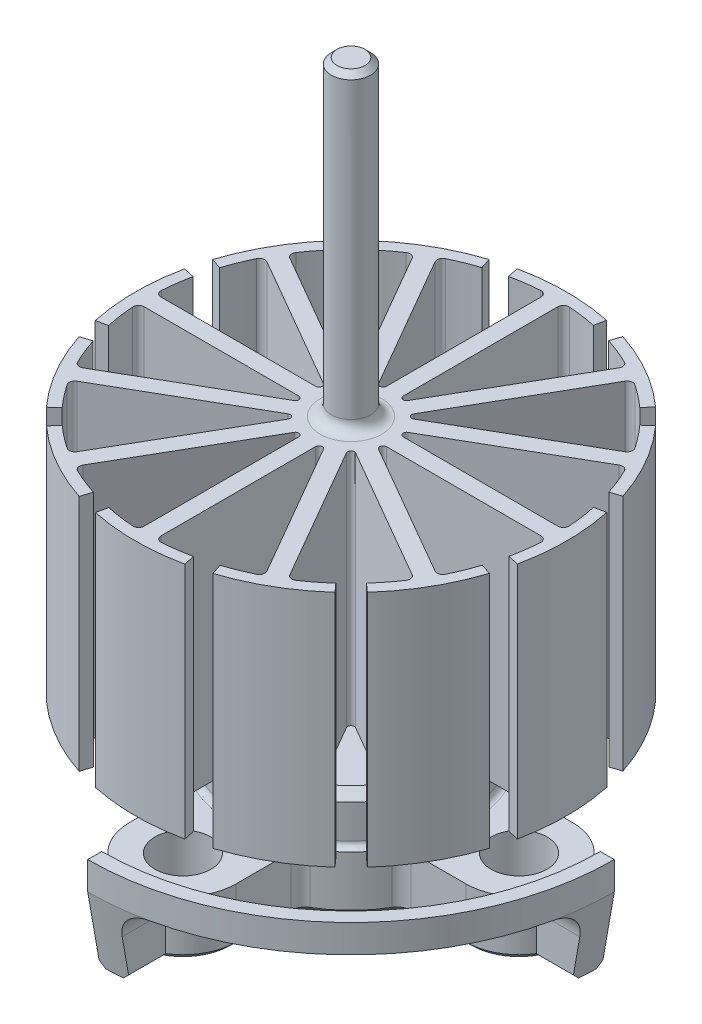
SolidWorks part; units mm, degrees
material "Ti-6Al-4V Solución tratada y envejecida (SS)"
ref_plane "Alzado" through (0, 0, 0) normal (0, 0, 1) x (1, 0, 0)
ref_plane "Planta" through (0, 0, 0) normal (0, 1, 0) x (1, 0, 0)
ref_plane "Vista lateral" through (0, 0, 0) normal (1, 0, 0) x (0, 0, -1)
sketch "Croquis1" plane through (0, 0, 0) normal (0, 0, 1) x (1, 0, 0)
  line L0 (0, 37.6231) -> (0, -37.6231) construction
  line L1 (0, -9.515) -> (0, 9.515) construction
  line L2 (9.515, 0) -> (-9.515, 0) construction
  line L3 (7.9, 0) -> (7.9, 2)
  line L4 (7.9, 2) -> (4.2, 2)
  line L5 (4, 2.2) -> (4, 3.4)
  line L6 (4, 3.4) -> (3.7, 3.7)
  line L7 (3.7, 3.7) -> (0.75, 3.7)
  line L8 (0.7, 12.9) -> (0.7, 23.6)
  line L9 (0.7, 23.6) -> (0, 23.6)
  line L10 (0, 23.6) -> (0, -1.4)
  line L11 (0.7, 0) -> (7.9, 0)
  line L12 (0.7, 0) -> (0.7, -0.2)
  line L13 (0.7, -0.2) -> (0.54, -0.2)
  line L14 (0.5, -0.24) -> (0.5, -0.41)
  line L15 (0.54, -0.45) -> (1, -0.45)
  line L16 (1, -0.45) -> (1, -1.2)
  line L17 (0.8, -1.4) -> (0, -1.4)
  line L18 (0.7, 3.75) -> (0.7, 3.95)
  line L19 (0.75, 4) -> (7.7, 4)
  line L20 (7.7, 4) -> (7.7, 12.5)
  line L21 (7.7, 12.5) -> (1.1, 12.5)
  arc A0 (4.2, 2) -> (4, 2.2) centre (4.2, 2.2) cw
  arc A1 (0.75, 3.7) -> (0.7, 3.75) centre (0.75, 3.75) cw
  arc A2 (0.54, -0.2) -> (0.5, -0.24) centre (0.54, -0.24) ccw
  arc A3 (0.5, -0.41) -> (0.54, -0.45) centre (0.54, -0.41) ccw
  arc A4 (1, -1.2) -> (0.8, -1.4) centre (0.8, -1.2) cw
  arc A5 (0.7, 3.95) -> (0.75, 4) centre (0.75, 3.95) cw
  arc A6 (0.7, 12.9) -> (1.1, 12.5) centre (1.1, 12.9) ccw
  point P5 (0, 0)
  dimension "D4" = 0.2
  dimension "D5" = 0.05
  dimension "D13" = 0.04
  dimension "D17" = 0.2
  dimension "D22" = 0.4
  dimension "D1" = 15.8
  dimension "D3" = 8
  dimension "D6" = 2
  dimension "D7" = 0.3
  dimension "D8" = 0.3
  dimension "D9" = 25
  dimension "D10" = 1.4
  dimension "D11" = 0.2
  dimension "D12" = 0.25
  dimension "D14" = 2
  dimension "D15" = 1
  dimension "D16" = 1.4
  dimension "D18" = 4
  dimension "D19" = 0.3
  dimension "D20" = 8.5
  dimension "D21" = 1.4
  dimension "D23" = 15.4
revolve "Revolución1" add sketch "Croquis1" angle 360 about L0
sketch "Croquis2" plane through (0, 12.5, 0) normal (0, 1, 0) x (1, 0, 0)
  line L0 (0, 0) -> (7.7, 0) construction
  line L1 (-9.515, 0) -> (9.515, 0) construction
  line L2 (0, 0) -> (6.6684, -3.85) construction
  line L3 (0, 0) -> (3.85, -6.6684) construction
  line L4 (0, 0) -> (0, -7.7) construction
  line L5 (0, 0) -> (-3.85, -6.6684) construction
  line L6 (0, 0) -> (-6.6684, -3.85) construction
  line L7 (0, 0) -> (-7.7, 0) construction
  line L8 (0, 0) -> (-6.6684, 3.85) construction
  line L9 (0, 0) -> (-3.85, 6.6684) construction
  line L10 (0, 0) -> (0, 7.7) construction
  line L11 (0, 0) -> (3.85, 6.6684) construction
  line L12 (0, 0) -> (6.6684, 3.85) construction
  line L13 (6.2835, 3.2814) -> (1.5044, 0.5221)
  line L14 (1.5639, 0.3) -> (7.0824, 0.3)
  line L15 (7.3201, 2.3887) -> (6.9398, 2.2647)
  line L16 (7.5319, 1.6) -> (7.1407, 1.5169)
  circle A0 centre (0, 0) radius 7.7 construction
  arc A1 (1.299, 0.75) -> (1.5, 0) centre (0, 0) ccw construction
  arc A2 (7.2819, 0.5141) -> (7.1407, 1.5169) centre (0, 0) ccw
  arc A4 (6.9398, 2.2647) -> (6.5633, 3.1957) centre (0, 0) ccw
  arc A5 (7.5319, 1.6) -> (7.3201, 2.3887) centre (0, 0) ccw
  arc A6 (1.5, 0) -> (1.299, 0.75) centre (0, 0) ccw construction
  arc A7 (1.5044, 0.5221) -> (1.5639, 0.3) centre (1.5639, 0.419) ccw
  arc A8 (7.0824, 0.3) -> (7.2819, 0.5141) centre (7.0824, 0.5) ccw
  arc A9 (6.2835, 3.2814) -> (6.5633, 3.1957) centre (6.3835, 3.1082) cw
  point P21 (0, 0)
  dimension "D2" = 3
  dimension "D8" = 0.2
  dimension "D3" = 0.3
  dimension "D4" = 0.3
  dimension "D5" = 1.6
  dimension "D6" = 1.6
  dimension "D7" = 0.4
  dimension "D1" = 12
extrude "Cortar-Extruir1" cut sketch "Croquis2" against normal up to surface (8.8 mm away) up to face at (0, 3.7, 0.75)
pattern_circular "MatrizC2" count 12 over 360 about axis through (0, 12.5, 0) along (0, 1, 0) of "Cortar-Extruir1"
sketch "Croquis6" plane through (0, 0, 0) normal (0, 0, 1) x (1, 0, 0)
  line L0 (9.4, 2.5) -> (8.9592, 0)
  line L1 (9.4, 3.5) -> (8.9, 3.5)
  line L2 (8.9, 3.5) -> (8.3557, 2.2943)
  line L3 (9.4, 3.5) -> (9.4, 2.5)
  line L4 (7.9, 2) -> (7.9, 0)
  line L6 (7.9, 0) -> (8.9592, 0)
  line L7 (7.5338, 4) -> (7.1424, 4) construction
  line L8 (0, -1.4) -> (0, 3.6979) construction
  line L9 (-0.8, -1.4) -> (0.8, -1.4) construction
  line L11 (0, -9.515) -> (0, 9.515) construction
  line L12 (9.515, 0) -> (-9.515, 0) construction
  arc A0 (8.3557, 2.2943) -> (7.9, 2) centre (7.9, 2.5) cw
  point P2 (9.15, 3.5)
  dimension "D4" = 0.5
  dimension "D1" = 3.5
  dimension "D2" = 0.5
  dimension "D3" = 0.5
  dimension "D5" = 1.0592
  dimension "D6" = 18.8
  dimension "D7" = 2
  dimension "D8" = 15.8
  dimension "D9" = 80
  dimension "D10" = 1
revolve "Revolución4" add sketch "Croquis6" angle 360 about L8
sketch "Croquis4" plane through (0, 0, 0) normal (0, -1, 0) x (1, 0, 0)
  line L0 (6, 1.9) -> (4.041, 1.9) construction
  line L1 (6, -1.9) -> (4.041, -1.9)
  line L2 (1.9, -6) -> (1.9, -4.041)
  line L3 (-1.9, -6) -> (-1.9, -4.041)
  line L4 (-6, -1.9) -> (-4.041, -1.9)
  line L5 (-6, 1.9) -> (-4.041, 1.9)
  line L6 (-1.9, 6) -> (-1.9, 4.041)
  line L7 (1.9, 6) -> (1.9, 4.041) construction
  line L10 (0, 7.9) -> (0, 9.4)
  line L11 (7.9, 0) -> (9.4, 0)
  circle A0 centre (0, 0) radius 6 construction
  circle A1 centre (6, 0) radius 1 construction
  arc A2 (6, -1.9) -> (6, 1.9) centre (6, 0) ccw construction
  arc A3 (3.6111, 2.1447) -> (2.1447, 3.6111) centre (0, 0) ccw construction
  arc A4 (4.041, 1.9) -> (3.6111, 2.1447) centre (4.041, 2.4) cw construction
  arc A5 (4.041, -1.9) -> (3.6111, -2.1447) centre (4.041, -2.4) ccw
  arc A6 (-1.9, -6) -> (1.9, -6) centre (0, -6) ccw
  arc A7 (2.1447, -3.6111) -> (3.6111, -2.1447) centre (0, 0) ccw
  arc A8 (1.9, -4.041) -> (2.1447, -3.6111) centre (2.4, -4.041) cw
  arc A9 (-1.9, -4.041) -> (-2.1447, -3.6111) centre (-2.4, -4.041) ccw
  circle A10 centre (0, -6) radius 1
  arc A11 (-6, 1.9) -> (-6, -1.9) centre (-6, 0) ccw
  arc A12 (-2.1447, 3.6111) -> (-3.6111, 2.1447) centre (0, 0) ccw
  arc A13 (-4.041, -1.9) -> (-3.6111, -2.1447) centre (-4.041, -2.4) cw
  arc A14 (-4.041, 1.9) -> (-3.6111, 2.1447) centre (-4.041, 2.4) ccw
  circle A15 centre (-6, 0) radius 1
  arc A16 (1.9, 6) -> (-1.9, 6) centre (0, 6) ccw construction
  arc A18 (-1.9, 4.041) -> (-2.1447, 3.6111) centre (-2.4, 4.041) cw
  arc A19 (1.9, 4.041) -> (2.1447, 3.6111) centre (2.4, 4.041) ccw construction
  circle A20 centre (0, 6) radius 1 construction
  arc A23 (-3.6111, -2.1447) -> (-2.1447, -3.6111) centre (0, 0) ccw
  arc A24 (-2.1447, 3.6111) -> (-3.6111, 2.1447) centre (0, 0) ccw [skipped]
  arc A27 (0, 7.9) -> (-1.9, 6) centre (0, 6) ccw
  arc A28 (6, -1.9) -> (7.9, 0) centre (6, 0) ccw
  circle A29 centre (0, 0) radius 9.4 construction
  arc A30 (0, 9.4) -> (9.4, 0) centre (0, 0) ccw
  point P46 (0, 0)
  dimension "D1" = 12
  dimension "D2" = 2
  dimension "D3" = 3.8
  dimension "D4" = 8.4
  dimension "D5" = 0.5
  dimension "D6" = 4
extrude "Cortar-Extruir3" cut sketch "Croquis4" against normal up to surface (3.5 mm away) up to face at (0, 3.5, -8.9)
sketch "Croquis7" plane through (0, 0, 0) normal (0, -1, 0) x (1, 0, 0)
  line L0 (6, 1.9) -> (4.041, 1.9) construction
  line L1 (1.9, 6) -> (1.9, 4.041) construction
  line L2 (6, 1.9) -> (4.041, 1.9)
  line L3 (1.9, 6) -> (1.9, 4.041)
  line L4 (1, 8.2957) -> (1, 7.6155)
  line L5 (0, 7.9) -> (0, 9.4) construction
  line L6 (8.2957, 1) -> (7.6155, 1)
  line L8 (7.9, 0) -> (9.4, 0) construction
  arc A0 (3.6111, 2.1447) -> (4.041, 1.9) centre (4.041, 2.4) ccw construction
  arc A1 (3.6111, 2.1447) -> (2.1447, 3.6111) centre (0, 0) ccw construction
  arc A2 (1.9, 4.041) -> (2.1447, 3.6111) centre (2.4, 4.041) ccw construction
  arc A3 (3.6111, 2.1447) -> (4.041, 1.9) centre (4.041, 2.4) ccw
  arc A4 (3.6111, 2.1447) -> (2.1447, 3.6111) centre (0, 0) ccw
  arc A5 (1.9, 4.041) -> (2.1447, 3.6111) centre (2.4, 4.041) ccw
  arc A7 (1.9, 6) -> (-1.9, 6) centre (0, 6) ccw construction
  arc A8 (1.9, 6) -> (1, 7.6155) centre (0, 6) ccw
  arc A9 (6, -1.9) -> (6, 1.9) centre (6, 0) ccw construction
  arc A10 (7.6155, 1) -> (6, 1.9) centre (6, 0) ccw
  arc A11 (8.2957, 1) -> (1, 8.2957) centre (0, 0) ccw
  circle A12 centre (0, 6) radius 1 construction
  circle A13 centre (0, 6) radius 1
  circle A14 centre (6, 0) radius 1 construction
  circle A15 centre (6, 0) radius 1
  arc A16 (8.9592, 0) -> (0, 8.9592) centre (0, 0) ccw construction
  arc A17 (8.3557, 0) -> (0, 8.3557) centre (0, 0) ccw construction
  dimension "D1" = 1
  dimension "D2" = 1
extrude "Cortar-Extruir4" cut sketch "Croquis7" against normal up to surface (3.5 mm away) up to face at (5.5225, 3.5, 5.5225)
ref_plane "Plano1" through (4.6478, 0, 4.6478) normal (0.7071, 0, 0.7071) x (0.7071, 0, -0.7071)
sketch "Croquis10" plane through (0, 0, 0) normal (0, -1, 0) x (1, 0, 0)
  line L0 (1, 8.2957) -> (1, 9.4957)
  line L1 (8.2957, 1) -> (9.4957, 1)
  arc A1 (8.2957, 1) -> (1, 8.2957) centre (0, 0) ccw construction
  arc A2 (8.2957, 1) -> (1, 8.2957) centre (0, 0) ccw
  arc A3 (9.4957, 1) -> (1, 9.4957) centre (0, 0) ccw
  arc A4 (8.9592, 0) -> (0, 8.9592) centre (0, 0) ccw construction
  dimension "D1" = 1.2
extrude "Cortar-Extruir7" cut sketch "Croquis10" against normal blind 2.5
fillet "Redondeo2" radius 1 2 edges at (8.8679, 2.5, 1) (1, 2.5, 8.8679)
fillet "Redondeo1" radius 1 2 edges at (7.9, 1, 0) (0, 1, 7.9)
chamfer "Chaflán2" distance 0.2 angle 45 1 edges at (0, 23.6, 0.7)
chamfer "Chaflán4" distance 0.2 angle 45 32 edges at (8.2594, 0, 1) (1, 0, 8.2594) (1.6598, 0, 6.9247) (1.9, 0, 5.0205) (1.9655, 0, 3.7937) (2.9698, 0, 2.9698) (3.7937, 0, 1.9655) (6.9247, 0, 1.6598) (5.0205, 0, 1.9) (8.8407, 0, 0) (8.1498, 0, -0.18) (7.0875, 0, -1.558) (5.0205, 0, -1.9) (3.7937, 0, -1.9655) (2.9698, 0, -2.9698) (1.9655, 0, -3.7937) (1.9, 0, -5.0205) (0, 0, -7.9) (-1.9, 0, -5.0205) (-1.9655, 0, -3.7937) (-2.9698, 0, -2.9698) (-3.7937, 0, -1.9655) (-5.0205, 0, -1.9) (-7.9, 0, 0) (-5.0205, 0, 1.9) (-3.7937, 0, 1.9655) (-2.9698, 0, 2.9698) (-1.9655, 0, 3.7937) (-1.9, 0, 5.0205) (0, 0, 8.8407) (-1.558, 0, 7.0875) (-0.18, 0, 8.1498)
equation "\"D4@Croquis2\"=\"D3@Croquis2\""
equation "\"D6@Croquis2\"=\"D5@Croquis2\""
equation "\"D2@Croquis7\"=\"D1@Croquis7\""
